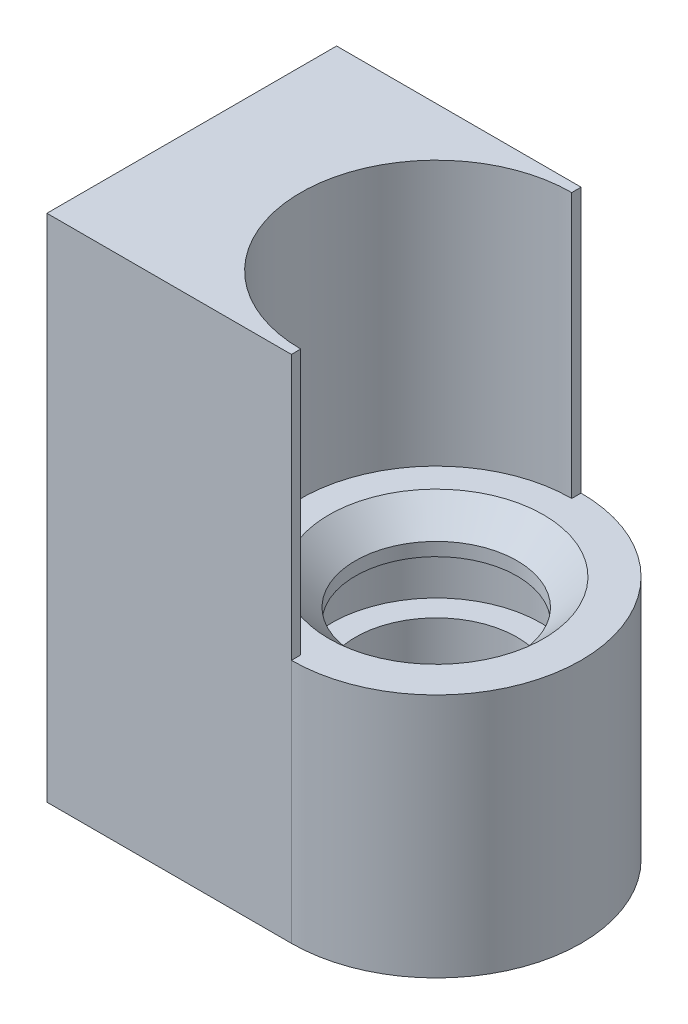
SolidWorks part; units mm, degrees
ref_plane "Front Plane" through (0, 0, 0) normal (0, 0, 1) x (1, 0, 0)
ref_plane "Top Plane" through (0, 0, 0) normal (0, 1, 0) x (1, 0, 0)
ref_plane "Right Plane" through (0, 0, 0) normal (1, 0, 0) x (0, 0, -1)
sketch "Sketch1" plane through (0, 0, 0) normal (0, 0, 1) x (1, 0, 0)
  line L0 (0, 0) -> (0, 6)
  line L1 (0, 6) -> (1.8335, 6)
  line L2 (1.8335, 6) -> (1.8335, 11.5)
  line L3 (1.8335, 11.5) -> (0, 11.5)
  line L4 (0, 11.5) -> (0, 15.5)
  line L5 (0, 15.5) -> (1.8335, 15.5)
  line L6 (1.8335, 15.5) -> (1.8335, 16.5)
  line L7 (-0.1665, 18.5) -> (-3, 18.5)
  line L8 (-3, 18.5) -> (-3, 0)
  line L9 (-3, 0) -> (0, 0)
  line L10 (7.9335, 6) -> (7.9335, 11.5) construction
  line L11 (1.8335, 16.5) -> (-0.1665, 18.5)
  point P9 (1.8335, 18.5)
  dimension "D1" = 5.5
  dimension "D2" = 4
  dimension "D3" = 6.1
  dimension "D4" = 6
  dimension "D5" = 3
  dimension "D6" = 3
revolve "Revolve1" add sketch "Sketch1" angle 360 about L10
sketch "Sketch2" plane through (0, 18.5, 0) normal (0, 1, 0) x (1, 0, 0)
  line L0 (7.9335, 10.9335) -> (-10.5202, 10.9335)
  line L1 (-10.5202, 10.9335) -> (-10.5202, -10.9335)
  line L2 (-10.5202, -10.9335) -> (7.9335, -10.9335)
  line L3 (7.9335, 10.9335) -> (7.9335, 10.2281)
  line L4 (7.9335, -10.2281) -> (7.9335, -10.9335)
  circle A0 centre (7.9335, 0) radius 10.9335 construction
  arc A3 (7.9335, 10.2281) -> (7.9335, -10.2281) centre (7.9335, 0) ccw
extrude "Boss-Extrude1" add sketch "Sketch2" against normal up to surface (18.5 mm away) and the other way blind 20 up to face at (7.9335, 0, -7.9335)
